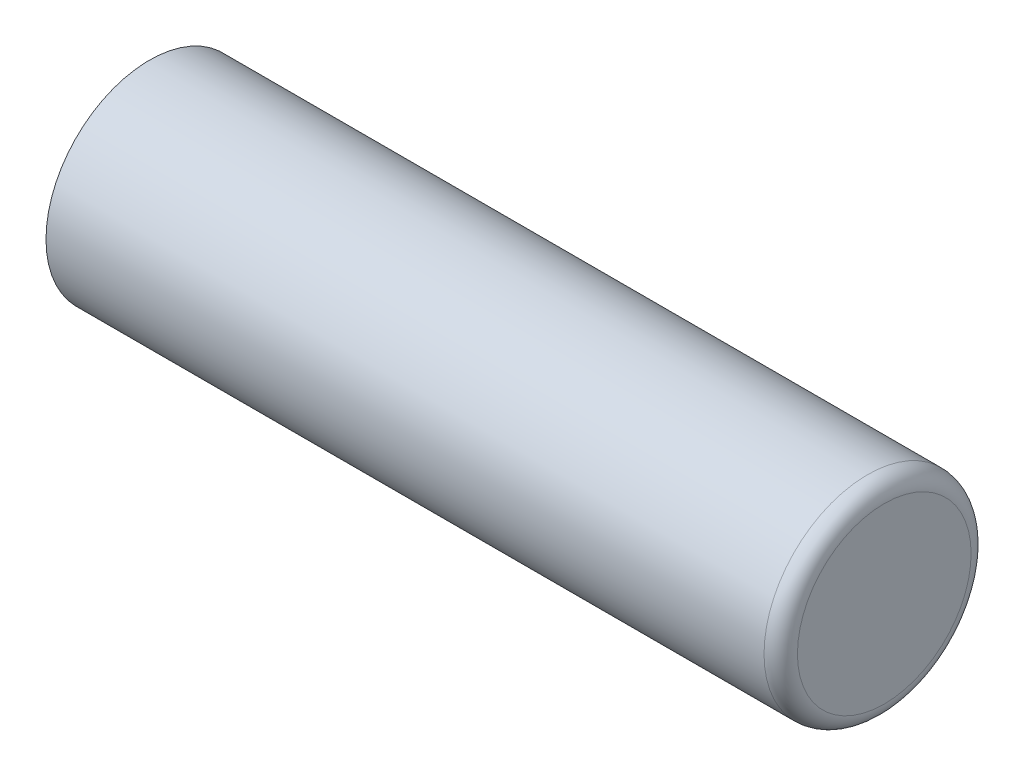
SolidWorks part; units mm, degrees
material "Plain Carbon Steel"
ref_plane "Front Plane" through (0, 0, 0) normal (0, 0, 1) x (1, 0, 0)
ref_plane "Top Plane" through (0, 0, 0) normal (0, 1, 0) x (1, 0, 0)
ref_plane "Right Plane" through (0, 0, 0) normal (1, 0, 0) x (0, 0, -1)
sketch "Sketch1" plane through (0, 0, 0) normal (0, 1, 0) x (1, 0, 0)
  line L1 (-11, 3.1) -> (10.5, 3.1)
  line L2 (-11, 3.1) -> (-11, 0)
  line L3 (-11, 0) -> (11, 0)
  line L4 (11, 2.6) -> (11, 0)
  line L5 (-11, 3.1) -> (11, 0) construction
  line L6 (-11, 0) -> (11, 3.1) construction
  arc A0 (10.5, 3.1) -> (11, 2.6) centre (10.5, 2.6) cw
  point P0 (0, 1.55)
  dimension "D3" = 0.5
  dimension "D1" = 3.1
  dimension "D2" = 22
revolve "Revolve1" add sketch "Sketch1" angle 360 about L3
sketch "Sketch2" plane through (-11, 0, 0) normal (-1, 0, 0) x (0, 0, 1)
  line L0 (0, 1) -> (0, -1) construction
  point P0 (0, 1)
  point P1 (0, -1)
  dimension "D1" = 2
other "CPoint1" parameters "Diameter"=2, "StubLength"=0
ref_axis "Axis1" through (-21, 1, 0) along (1, 0, 0)
other "CPoint2" parameters "Diameter"=2, "StubLength"=0
ref_axis "Axis2" through (-21, -1, 0) along (1, 0, 0)
